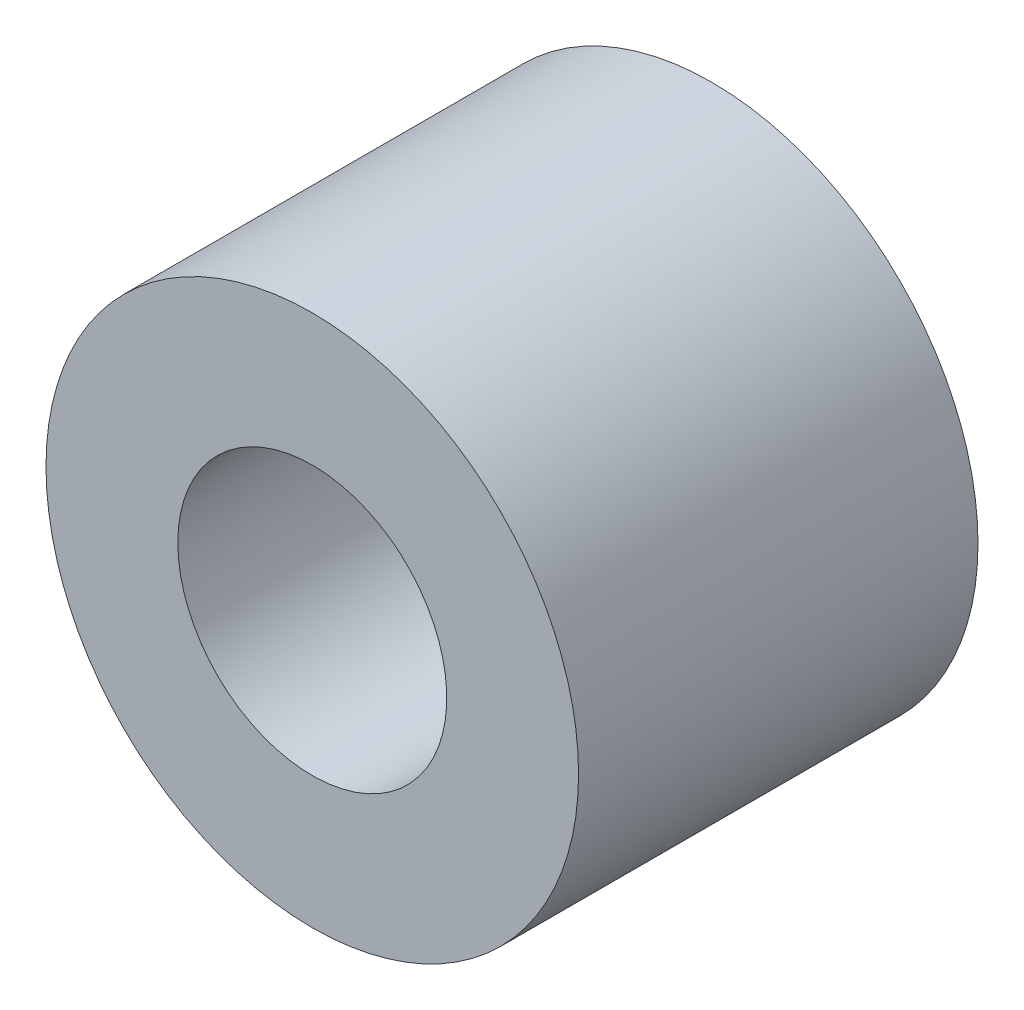
SolidWorks part; units mm, degrees
ref_plane "Front Plane" through (0, 0, 0) normal (0, 0, 1) x (1, 0, 0)
ref_plane "Top Plane" through (0, 0, 0) normal (0, 1, 0) x (1, 0, 0)
ref_plane "Right Plane" through (0, 0, 0) normal (1, 0, 0) x (0, 0, -1)
sketch "Sketch1" plane through (0, 0, 0) normal (0, 0, 1) x (1, 0, 0)
  circle A0 centre (0, 0) radius 12.7
  circle A1 centre (0, 0) radius 6.4135
  dimension "OD" = 25.4
  dimension "ID" = 12.827
extrude "Extrude1" add sketch "Sketch1" along normal mid plane 19.05
sketch "Sketch2" plane through (0, 0, 0) normal (1, 0, 0) x (0, 0, -1)
  line L0 (-9.525, -6.4135) -> (9.525, -6.4135) construction
  line L3 (9.525, 6.4135) -> (-9.525, 6.4135) construction
  line L5 (-9.525, -6.4135) -> (9.525, -6.4135)
  line L6 (9.525, 6.4135) -> (-9.525, 6.4135)
sketch "Sketch4" plane through (0, 0, 9.525) normal (0, 0, 1) x (1, 0, 0)
  line L0 (0, 0) -> (-4.535, 4.535)
  line L1 (0, -2.6194) -> (0, 2.6194) construction
  circle A0 centre (0, 0) radius 6.4135 construction
  dimension "D1" = 45
